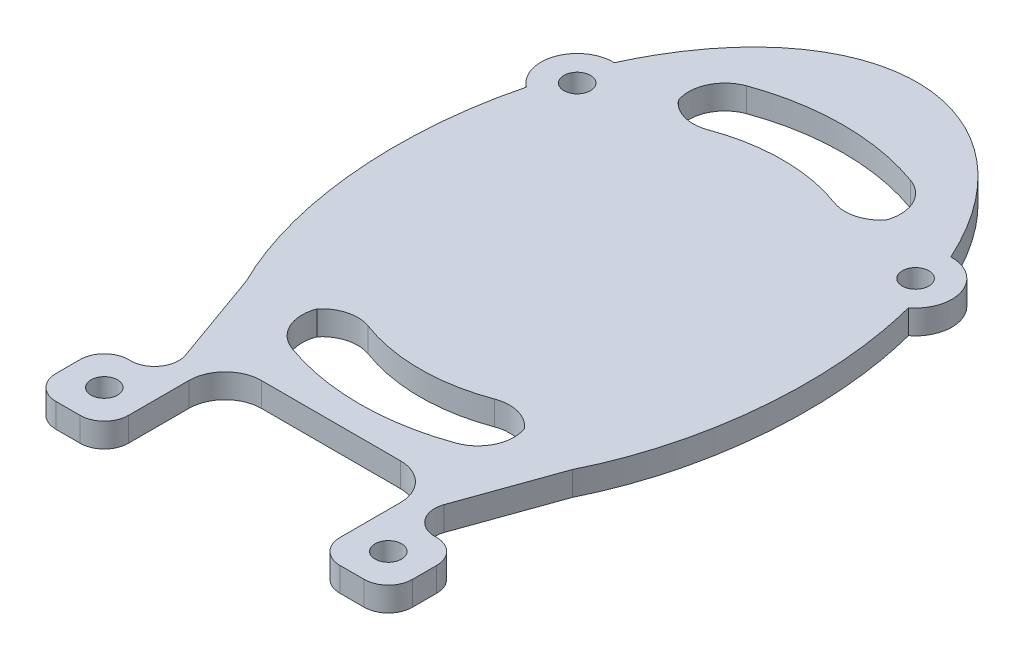
SolidWorks part; units mm, degrees
material "Thornel Mat VMA"
ref_plane "Front Plane" through (0, 0, 0) normal (0, 0, 1) x (1, 0, 0)
ref_plane "Top Plane" through (0, 0, 0) normal (0, 1, 0) x (1, 0, 0)
ref_plane "Right Plane" through (0, 0, 0) normal (1, 0, 0) x (0, 0, -1)
sketch "Sketch1" plane through (0, 0, 0) normal (0, 1, 0) x (1, 0, 0)
  line L0 (-13.5, -15.8768) -> (13.5, -15.8768) construction
  line L1 (-17, 0) -> (17, 0) construction
  line L2 (0, 26.1232) -> (0, -26.1232) construction
  line L4 (-13.5, -15.8768) -> (-8.75, -26.3768) construction
  line L7 (-14.75, -32.3768) -> (-8.75, -32.3768)
  line L8 (-14.75, -32.3768) -> (-14.75, -26.3768)
  line L10 (-8.75, -32.3768) -> (-8.75, -26.3768)
  line L11 (-14.75, -32.3768) -> (-8.75, -26.3768) construction
  line L12 (-14.75, -26.3768) -> (-8.75, -32.3768) construction
  line L14 (14.75, -26.3768) -> (8.75, -32.3768) construction
  line L15 (14.75, -32.3768) -> (8.75, -26.3768) construction
  line L16 (8.75, -26.3768) -> (13.5, -15.8768) construction
  line L18 (8.75, -32.3768) -> (8.75, -26.3768)
  line L19 (14.75, -32.3768) -> (14.75, -26.3768)
  line L20 (14.75, -32.3768) -> (8.75, -32.3768)
  line L22 (-8.75, -26.3768) -> (8.75, -26.3768)
  line L25 (13.5, -15.8768) -> (9.75, -26.3768)
  line L26 (9.75, -26.3768) -> (14.75, -26.3768)
  line L27 (-13.5, -15.8768) -> (-9.75, -26.3768)
  line L28 (-9.75, -26.3768) -> (-14.75, -26.3768)
  circle A0 centre (-11.75, -29.3768) radius 1.1
  circle A1 centre (11.75, -29.3768) radius 1.1
  ellipse E0 centre (0, 0) end of major axis (0, -26.1232) minor radius 17 (-13.5, -15.8768) -> (13.5, -15.8768) cw
  point P1 (-11.75, -29.3768)
  point P22 (11.75, -29.3768)
  dimension "D4" = 6
  dimension "D7" = 2.2
  dimension "D10" = 2.2
  dimension "D1" = 34
  dimension "D2" = 27
  dimension "D3" = 42
  dimension "D5" = 1
  dimension "D6" = 1
  dimension "D8" = 10.5
  dimension "D9" = 4.75
extrude "Boss-Extrude1" add sketch "Sketch1" along normal blind 2
sketch "Sketch2" plane through (0, 2, 0) normal (0, 1, 0) x (1, 0, 0)
  line L0 (-17, 0) -> (17, 0) construction
  line L1 (-11.76, 0) -> (-11.76, 18.8642) construction
  line L2 (0, 26.1232) -> (0, 0) construction
  circle A1 centre (-14, 12) radius 3
  circle A2 centre (14, 12) radius 3
  ellipse E0 centre (0, 0) end of major axis (0, -26.1232) minor radius 17 (13.5, -15.8768) -> (-13.5, -15.8768) ccw construction
  dimension "D2" = 6
  dimension "D3" = 12
  dimension "D4" = 5.24
  dimension "D5" = 14
extrude "Boss-Extrude2" add sketch "Sketch2" against normal up to surface (2 mm away) up to face at (-11.75, 0, 30.4768)
sketch "Sketch3" plane through (0, 2, 0) normal (0, 1, 0) x (1, 0, 0)
  line L0 (10, 17.3205) -> (7.5, 12.9904)
  line L1 (-7.5, 12.9904) -> (-10, 17.3205)
  line L2 (0, 0) -> (10, 17.3205) construction
  line L3 (0, 0) -> (-10, 17.3205) construction
  line L4 (0, 15) -> (0, 0) construction
  line L5 (0, 15) -> (0, 26.1232) construction
  line L6 (-17, 0) -> (17, 0) construction
  line L7 (-7.5, -12.9904) -> (-10, -17.3205)
  line L8 (10, -17.3205) -> (7.5, -12.9904)
  arc A0 (7.5, 12.9904) -> (-7.5, 12.9904) centre (0, 0) ccw
  arc A1 (10, 17.3205) -> (-10, 17.3205) centre (0, 0) ccw
  arc A2 (10, -17.3205) -> (-10, -17.3205) centre (0, 0) cw
  arc A3 (7.5, -12.9904) -> (-7.5, -12.9904) centre (0, 0) cw
  ellipse E0 centre (0, 0) end of major axis (0, -26.1232) minor radius 17 (13.9186, 14.9989) -> (-13.9186, 14.9989) ccw construction
  ellipse E1 centre (0, 0) end of major axis (0, -26.1232) minor radius 17 (-15.8088, 9.6066) -> (-13.5, -15.8768) ccw construction
  ellipse E2 centre (0, 0) end of major axis (0, -26.1232) minor radius 17 (13.5, -15.8768) -> (15.8088, 9.6066) ccw construction
  dimension "D1" = 15
  dimension "D2" = 5
  dimension "D3" = 30
extrude "Cut-Extrude1" cut sketch "Sketch3" against normal up to next
fillet "Fillet2" radius 3 8 edges at (10, 1, -17.3205) (7.5, 1, -12.9904) (-7.5, 1, -12.9904) (-10, 1, -17.3205) (7.5, 1, 12.9904) (10, 1, 17.3205) (-10, 1, 17.3205) (-7.5, 1, 12.9904)
sketch "Sketch4" plane through (0, 2, 0) normal (0, 1, 0) x (1, 0, 0)
  line L6 (8.75, -22.3768) -> (-8.75, -22.3768)
  line L8 (8.75, -22.3768) -> (8.75, -26.3768)
  line L9 (8.75, -26.3768) -> (-8.75, -26.3768)
  line L10 (-8.75, -22.3768) -> (-8.75, -26.3768)
  line L11 (8.75, -22.3768) -> (-8.75, -26.3768) construction
  line L12 (8.75, -26.3768) -> (-8.75, -22.3768) construction
  point P0 (0, -24.3768)
  dimension "D1" = 4
extrude "Cut-Extrude2" cut sketch "Sketch4" against normal up to next
fillet "Fillet3" radius 3 2 edges at (8.75, 1, 22.3768) (-8.75, 1, 22.3768)
fillet "Fillet7" radius 2 8 edges at (9.75, 1, 26.3768) (14.75, 1, 26.3768) (14.75, 1, 32.3768) (8.75, 1, 32.3768) (-8.75, 1, 32.3768) (-14.75, 1, 32.3768) (-14.75, 1, 26.3768) (-9.75, 1, 26.3768)
sketch "Sketch5" plane through (0, 2, 0) normal (0, 1, 0) x (1, 0, 0)
  line L0 (0, 26.1232) -> (0, 0) construction
  circle A0 centre (-14, 12) radius 1.1
  arc A1 (-13.9186, 14.9989) -> (-15.8088, 9.6066) centre (-14, 12) ccw construction
  circle A2 centre (14, 12) radius 1.1
  ellipse E0 centre (0, 0) end of major axis (0, -26.1232) minor radius 17 (13.9186, 14.9989) -> (-13.9186, 14.9989) ccw construction
  dimension "D1" = 2.2
extrude "Cut-Extrude3" cut sketch "Sketch5" against normal up to next
